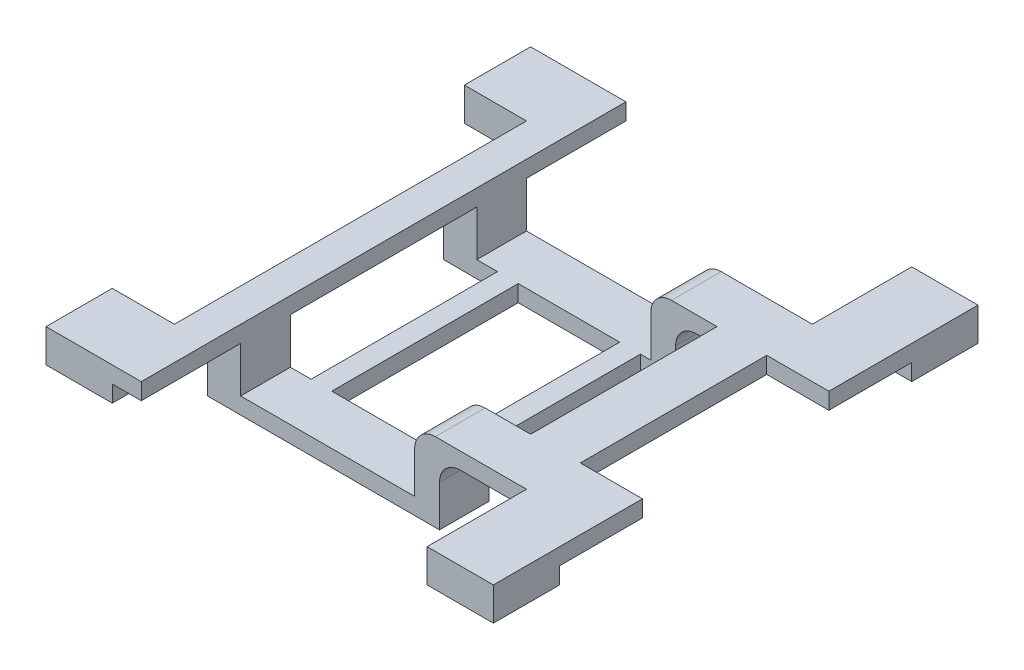
SolidWorks part; units mm, degrees
ref_plane "Front Plane" through (0, 0, 0) normal (0, 0, 1) x (1, 0, 0)
ref_plane "Top Plane" through (0, 0, 0) normal (0, 1, 0) x (1, 0, 0)
ref_plane "Right Plane" through (0, 0, 0) normal (1, 0, 0) x (0, 0, -1)
sketch "Sketch1" plane through (0, 0, 0) normal (0, 1, 0) x (1, 0, 0)
  line L1 (-56.5, 42.5) -> (56.5, 42.5)
  line L2 (-56.5, 42.5) -> (-56.5, -42.5)
  line L3 (-56.5, -42.5) -> (56.5, -42.5)
  line L4 (56.5, 42.5) -> (56.5, -42.5)
  line L5 (-56.5, 42.5) -> (56.5, -42.5) construction
  line L6 (-56.5, -42.5) -> (56.5, 42.5) construction
  point P0 (0, 0)
  dimension "D1" = 113
  dimension "D2" = 85
extrude "Boss-Extrude1" add sketch "Sketch1" along normal blind 4
sketch "Sketch4" plane through (0, 0, 0) normal (0, -1, 0) x (1, 0, 0)
  line L0 (-56.5, 42.5) -> (56.5, 42.5) construction
  line L5 (-56.5, 42.5) -> (-40.5, 42.5)
  line L6 (-56.5, 42.5) -> (-56.5, 58.5)
  line L7 (-56.5, 58.5) -> (-40.5, 58.5)
  line L8 (-40.5, 42.5) -> (-40.5, 58.5)
  line L9 (51.5, 42.5) -> (35.5, 42.5)
  line L10 (51.5, 42.5) -> (51.5, 58.5)
  line L11 (51.5, 58.5) -> (35.5, 58.5)
  line L12 (35.5, 42.5) -> (35.5, 58.5)
  line L18 (56.5, 42.5) -> (56.5, -42.5) construction
  line L19 (0, 0) -> (-56.5, 0) construction
  line L20 (-56.5, -42.5) -> (-56.5, 42.5) construction
  line L21 (51.5, -58.5) -> (35.5, -58.5)
  line L22 (35.5, -42.5) -> (35.5, -58.5)
  line L23 (51.5, -42.5) -> (35.5, -42.5)
  line L24 (51.5, -42.5) -> (51.5, -58.5)
  line L25 (-56.5, -58.5) -> (-40.5, -58.5)
  line L26 (-40.5, -42.5) -> (-40.5, -58.5)
  line L27 (-56.5, -42.5) -> (-40.5, -42.5)
  line L28 (-56.5, -42.5) -> (-56.5, -58.5)
  dimension "D1" = 16
  dimension "D2" = 16
  dimension "D3" = 5
  dimension "D4" = 16
  dimension "D5" = 16
extrude "Boss-Extrude3" add sketch "Sketch4" against normal up to surface (4 mm away) and the other way blind 1 up to face at (0, 4, 0)
sketch "Sketch10" plane through (0, 4, 0) normal (0, 1, 0) x (1, 0, 0)
  line L0 (-40.5, -58.5) -> (-56.5, -58.5) construction
  line L1 (-40.5, -42.5) -> (-30.5, -42.5)
  line L2 (-40.5, -42.5) -> (-40.5, -58.5)
  line L3 (-40.5, -58.5) -> (-30.5, -58.5)
  line L4 (-30.5, -42.5) -> (-30.5, -58.5)
  line L5 (-40.5, 42.5) -> (-30.5, 42.5)
  line L6 (-40.5, 42.5) -> (-40.5, 58.5)
  line L7 (-40.5, 58.5) -> (-30.5, 58.5)
  line L8 (-30.5, 42.5) -> (-30.5, 58.5)
  line L9 (-56.5, 58.5) -> (-40.5, 58.5) construction
  dimension "D1" = 10
  dimension "D2" = 10
extrude "Boss-Extrude6" add sketch "Sketch10" against normal up to surface (4 mm away) up to face at (9.3, 0, 0)
sketch "Sketch6" plane through (0, 4, 0) normal (0, 1, 0) x (1, 0, 0)
  line L0 (35.5, 42.5) -> (35.5, 58.5) construction
  line L1 (-31.5, 22.5) -> (41.5, 22.5)
  line L2 (-31.5, 22.5) -> (-31.5, -22.5)
  line L3 (-31.5, -22.5) -> (41.5, -22.5)
  line L4 (41.5, 22.5) -> (41.5, -22.5)
  line L5 (35.5, -58.5) -> (35.5, -42.5) construction
  line L6 (35.5, 42.5) -> (-30.5, 42.5) construction
  line L7 (-30.5, -42.5) -> (35.5, -42.5) construction
  line L8 (-56.5, 58.5) -> (-56.5, -58.5) construction
  line L9 (-41.5, 0) -> (-56.5, 0) construction
  line L10 (-56.5, 42.5) -> (-41.5, 42.5)
  line L11 (-56.5, 42.5) -> (-56.5, -42.5)
  line L12 (-56.5, -42.5) -> (-41.5, -42.5)
  line L13 (-41.5, 42.5) -> (-41.5, -42.5)
  line L14 (-31.5, 0) -> (41.5, 0) construction
  line L15 (-30.5, 42.5) -> (35.5, 42.5)
  line L16 (-30.5, 42.5) -> (-30.5, 34.5)
  line L17 (-30.5, 34.5) -> (35.5, 34.5)
  line L18 (35.5, 42.5) -> (35.5, 34.5)
  line L19 (-30.5, -42.5) -> (35.5, -42.5)
  line L20 (-30.5, -42.5) -> (-30.5, -34.5)
  line L21 (-30.5, -34.5) -> (35.5, -34.5)
  line L22 (35.5, -42.5) -> (35.5, -34.5)
  line L23 (56.5, -42.5) -> (56.5, 42.5) construction
  dimension "D1" = 20
  dimension "D2" = 20
  dimension "D3" = 25
  dimension "D4" = 15
  dimension "D5" = 85
  dimension "D6" = 8
  dimension "D7" = 8
  dimension "D8" = 15
extrude "Cut-Extrude2" cut sketch "Sketch6" against normal through all
sketch "Sketch8" plane through (0, -1, 0) normal (0, -1, 0) x (1, 0, 0)
  line L0 (-56.5, 58.5) -> (-40.5, 58.5) construction
  line L1 (-56.5, 58.5) -> (-56.5, 42.5) construction
  line L2 (-56.5, 42.5) -> (-40.5, 42.5) construction
  line L3 (-40.5, 58.5) -> (-40.5, 42.5) construction
  line L4 (35.5, 58.5) -> (51.5, 58.5) construction
  line L5 (35.5, 58.5) -> (35.5, 42.5) construction
  line L6 (35.5, 42.5) -> (51.5, 42.5) construction
  line L7 (51.5, 58.5) -> (51.5, 42.5) construction
  line L8 (-56.5, 58.5) -> (-40.5, 42.5) construction
  line L9 (-56.5, 42.5) -> (-40.5, 58.5) construction
  line L10 (35.5, 58.5) -> (51.5, 42.5) construction
  line L11 (35.5, 42.5) -> (51.5, 58.5) construction
  line L12 (51.5, 58.5) -> (35.5, 58.5) construction
  line L13 (0, 0) -> (-56.5, 0) construction
  line L14 (-56.5, 42.5) -> (-40.5, 42.5) construction
  line L15 (35.5, 42.5) -> (51.5, 42.5) construction
  circle A0 centre (-48.5, 50.5) radius 6.1
  circle A1 centre (43.5, 50.5) radius 6.1
  circle A2 centre (43.5, -50.5) radius 6.1
  circle A3 centre (-48.5, -50.5) radius 6.1
  dimension "D3" = 12.2
  dimension "D4" = 12.2
extrude "Cut-Extrude3" cut sketch "Sketch8" against normal blind 3.2
sketch "Sketch9" plane through (0, -1, 0) normal (0, -1, 0) x (1, 0, 0)
  line L0 (-55.5, 57.5) -> (-55.5, 43.5)
  line L1 (-56.5, 58.5) -> (-40.5, 58.5)
  line L2 (-56.5, 58.5) -> (-56.5, 42.5)
  line L3 (-56.5, 42.5) -> (-40.5, 42.5)
  line L4 (-40.5, 58.5) -> (-40.5, 42.5)
  line L5 (35.5, 58.5) -> (51.5, 58.5)
  line L6 (35.5, 58.5) -> (35.5, 42.5)
  line L7 (35.5, 42.5) -> (51.5, 42.5)
  line L8 (51.5, 58.5) -> (51.5, 42.5)
  line L9 (-55.5, 43.5) -> (-41.5, 43.5)
  line L10 (-41.5, 57.5) -> (-41.5, 43.5)
  line L11 (-55.5, 57.5) -> (-41.5, 57.5)
  line L16 (0, 0) -> (-56.5, 0) construction
  line L17 (36.5, -43.5) -> (50.5, -43.5)
  line L18 (36.5, -57.5) -> (36.5, -43.5)
  line L19 (50.5, -57.5) -> (36.5, -57.5)
  line L20 (50.5, 43.5) -> (50.5, 57.5)
  line L21 (50.5, 57.5) -> (36.5, 57.5)
  line L22 (36.5, 57.5) -> (36.5, 43.5)
  line L23 (36.5, 43.5) -> (50.5, 43.5)
  line L24 (50.5, 43.5) -> (50.5, 57.5)
  line L25 (50.5, 57.5) -> (36.5, 57.5)
  line L26 (36.5, 57.5) -> (36.5, 43.5)
  line L27 (36.5, 43.5) -> (50.5, 43.5)
  line L28 (50.5, -43.5) -> (50.5, -57.5)
  line L29 (-55.5, -57.5) -> (-41.5, -57.5)
  line L30 (-41.5, -57.5) -> (-41.5, -43.5)
  line L31 (-55.5, -43.5) -> (-41.5, -43.5)
  line L32 (51.5, -58.5) -> (51.5, -42.5)
  line L33 (35.5, -42.5) -> (51.5, -42.5)
  line L34 (35.5, -58.5) -> (35.5, -42.5)
  line L35 (35.5, -58.5) -> (51.5, -58.5)
  line L36 (-40.5, -58.5) -> (-40.5, -42.5)
  line L37 (-56.5, -42.5) -> (-40.5, -42.5)
  line L38 (-56.5, -58.5) -> (-56.5, -42.5)
  line L39 (-56.5, -58.5) -> (-40.5, -58.5)
  line L40 (-55.5, -57.5) -> (-55.5, -43.5)
  dimension "D1" = 1
  dimension "D2" = 1
extrude "Boss-Extrude5" add sketch "Sketch9" along normal blind 3
fillet "Fillet1" radius 0.2 4 edges at (43.5, -1, -44.4) (-48.5, -1, -44.4) (43.5, -1, 44.4) (-48.5, -1, 44.4)
sketch "Sketch13" plane through (56.5, 0, 0) normal (1, 0, 0) x (0, 0, -1)
  line L1 (-42.5, 4) -> (42.5, 4)
  line L2 (-42.5, 4) -> (-42.5, 0)
  line L3 (-42.5, 0) -> (42.5, 0)
  line L4 (42.5, 4) -> (42.5, 0)
extrude "Cut-Extrude4" cut sketch "Sketch13" against normal up to surface (5 mm away) up to face at (51.5, 0, 48.9)
sketch "Sketch14" plane through (0, 4, 0) normal (0, 1, 0) x (1, 0, 0)
  line L0 (-41.5, -42.5) -> (-41.5, 42.5) construction
  line L1 (-41.5, 22.5) -> (51.5, 22.5)
  line L2 (-41.5, 22.5) -> (-41.5, -22.5)
  line L3 (-41.5, -22.5) -> (51.5, -22.5)
  line L4 (51.5, 22.5) -> (51.5, -22.5)
  line L5 (51.5, 58.5) -> (51.5, -58.5) construction
  line L6 (-31.5, -22.5) -> (41.5, -22.5) construction
  line L7 (41.5, 22.5) -> (-31.5, 22.5) construction
extrude "Cut-Extrude5" cut sketch "Sketch14" against normal through all
sketch "Sketch15" plane through (0, 4, 0) normal (0, 1, 0) x (1, 0, 0)
  line L0 (51.5, 22.5) -> (-41.5, 22.5) construction
  line L1 (-28.5, 22.5) -> (-23.5, 22.5)
  line L2 (-28.5, 22.5) -> (-28.5, -22.5)
  line L3 (-28.5, -22.5) -> (-23.5, -22.5)
  line L4 (-23.5, 22.5) -> (-23.5, -22.5)
  line L5 (-41.5, -22.5) -> (51.5, -22.5) construction
  line L6 (51.5, -22.5) -> (51.5, -58.5) construction
  line L7 (24.5, 22.5) -> (36.5, 22.5)
  line L8 (24.5, 22.5) -> (24.5, -22.5)
  line L9 (24.5, -22.5) -> (36.5, -22.5)
  line L10 (36.5, 22.5) -> (36.5, -22.5)
  line L11 (-41.5, -42.5) -> (-41.5, -22.5) construction
  dimension "D1" = 5
  dimension "D2" = 12
  dimension "D3" = 15
  dimension "D4" = 13
extrude "Boss-Extrude7" add sketch "Sketch15" against normal up to surface (4 mm away) up to face at (-5.1, 0, 40.1)
sketch "Sketch16" plane through (0, 0, 0) normal (0, -1, 0) x (1, 0, 0)
  line L24 (24.5, 22.5) -> (24.5, -22.5) construction
  line L25 (24.5, -22.5) -> (-23.5, -22.5) construction
  line L26 (-23.5, -22.5) -> (-23.5, 22.5) construction
  line L27 (-23.5, 22.5) -> (24.5, 22.5) construction
  line L28 (24.5, 22.5) -> (24.5, -22.5) construction
  line L29 (24.5, -22.5) -> (-23.5, -22.5) construction
  line L30 (-23.5, -22.5) -> (-23.5, 22.5)
  line L31 (-23.5, 22.5) -> (24.5, 22.5) construction
  line L36 (-30.5, -34.5) -> (14.5, -34.5)
  line L37 (14.5, -34.5) -> (14.5, -22.5)
  line L38 (14.5, -22.5) -> (-23.5, -22.5)
  line L39 (-23.5, 22.5) -> (14.5, 22.5)
  line L40 (14.5, 22.5) -> (14.5, 34.5)
  line L41 (14.5, 34.5) -> (-30.5, 34.5)
  line L42 (-28.5, 22.5) -> (-41.5, 22.5)
  line L43 (-41.5, 22.5) -> (-28.5, 22.5) construction
  line L44 (-41.5, 22.5) -> (-41.5, 34.5)
  line L45 (-41.5, 34.5) -> (-30.5, 34.5)
  line L46 (-28.5, -22.5) -> (-41.5, -22.5)
  line L47 (-28.5, -22.5) -> (-41.5, -22.5) construction
  line L48 (-41.5, 42.5) -> (-41.5, 22.5)
  line L49 (-41.5, 22.5) -> (-28.5, 22.5)
  line L50 (-28.5, 22.5) -> (-28.5, -22.5)
  line L51 (-28.5, -22.5) -> (-41.5, -22.5)
  line L52 (-41.5, -22.5) -> (-41.5, -42.5)
  line L53 (-41.5, -42.5) -> (-40.5, -42.5)
  line L54 (-40.5, -42.5) -> (-40.5, -58.5)
  line L55 (-40.5, -58.5) -> (-30.5, -58.5)
  line L56 (-30.5, -58.5) -> (-30.5, -34.5)
  line L57 (-30.5, -34.5) -> (35.5, -34.5)
  line L58 (35.5, -34.5) -> (35.5, -42.5)
  line L59 (35.5, -42.5) -> (51.5, -42.5)
  line L60 (51.5, -42.5) -> (51.5, -22.5)
  line L61 (51.5, -22.5) -> (36.5, -22.5)
  line L62 (36.5, -22.5) -> (36.5, 22.5)
  line L63 (36.5, 22.5) -> (51.5, 22.5)
  line L64 (51.5, 22.5) -> (51.5, 42.5)
  line L65 (51.5, 42.5) -> (35.5, 42.5)
  line L66 (35.5, 42.5) -> (35.5, 34.5)
  line L67 (35.5, 34.5) -> (-30.5, 34.5)
  line L68 (-30.5, 34.5) -> (-30.5, 58.5)
  line L69 (-30.5, 58.5) -> (-40.5, 58.5)
  line L70 (-40.5, 58.5) -> (-40.5, 42.5)
  line L71 (-40.5, 42.5) -> (-41.5, 42.5)
  line L72 (-41.5, 42.5) -> (-41.5, 22.5) construction
  line L74 (-28.5, 22.5) -> (-28.5, -22.5)
  line L76 (-41.5, -22.5) -> (-41.5, -42.5) construction
  line L77 (-41.5, -42.5) -> (-40.5, -42.5) construction
  line L78 (-40.5, -42.5) -> (-40.5, -58.5) construction
  line L79 (-40.5, -58.5) -> (-30.5, -58.5) construction
  line L80 (-30.5, -58.5) -> (-30.5, -34.5) construction
  line L81 (-30.5, -34.5) -> (35.5, -34.5) construction
  line L82 (35.5, -34.5) -> (35.5, -42.5) construction
  line L83 (35.5, -42.5) -> (51.5, -42.5) construction
  line L84 (51.5, -42.5) -> (51.5, -22.5) construction
  line L85 (51.5, -22.5) -> (36.5, -22.5) construction
  line L86 (36.5, -22.5) -> (36.5, 22.5) construction
  line L87 (36.5, 22.5) -> (51.5, 22.5) construction
  line L88 (51.5, 22.5) -> (51.5, 42.5) construction
  line L89 (51.5, 42.5) -> (35.5, 42.5) construction
  line L90 (35.5, 42.5) -> (35.5, 34.5) construction
  line L91 (35.5, 34.5) -> (-30.5, 34.5) construction
  line L92 (-30.5, 34.5) -> (-30.5, 58.5) construction
  line L93 (-30.5, 58.5) -> (-40.5, 58.5) construction
  line L94 (-40.5, 58.5) -> (-40.5, 42.5) construction
  line L95 (-40.5, 42.5) -> (-41.5, 42.5) construction
  line L96 (-41.5, -22.5) -> (-41.5, -34.5)
  line L97 (-41.5, -34.5) -> (-30.5, -34.5)
  dimension "D2" = 45
  dimension "D1" = 0
extrude "Boss-Extrude8" add sketch "Sketch16" along normal blind 15
sketch "Sketch17" plane through (0, 4, 0) normal (0, 1, 0) x (1, 0, 0)
  line L0 (-30.5, -58.5) -> (-56.5, -58.5) construction
  line L1 (-33.5, 58.5) -> (8.5, 58.5)
  line L2 (-33.5, 58.5) -> (-33.5, -58.5)
  line L3 (-33.5, -58.5) -> (8.5, -58.5)
  line L4 (8.5, 58.5) -> (8.5, -58.5)
  line L7 (-41.5, 22.5) -> (-41.5, 42.5) construction
  line L8 (-56.5, 58.5) -> (-30.5, 58.5) construction
  dimension "D1" = 8
  dimension "D2" = 42
extrude "Cut-Extrude6" cut sketch "Sketch17" against normal blind 15
sketch "Sketch18" plane through (0, 4, 0) normal (0, 1, 0) x (1, 0, 0)
  line L1 (-33.5, 22.5) -> (-41.5, 22.5)
  line L2 (-33.5, 22.5) -> (-33.5, -22.5)
  line L3 (-33.5, -22.5) -> (-41.5, -22.5)
  line L4 (-41.5, 22.5) -> (-41.5, -22.5)
extrude "Boss-Extrude9" add sketch "Sketch18" against normal blind 4
fillet "Fillet2" radius 5 4 edges at (8.5, 4, -28.5) (8.5, 4, 28.5) (14.5, 0, 28.5) (14.5, 0, -28.5)
sketch "Sketch19" plane through (0, -11, 0) normal (0, 1, 0) x (1, 0, 0)
  line L0 (-23.5, 22.5) -> (8.5, 22.5) construction
  line L1 (1, 22.5) -> (6, 22.5)
  line L2 (1, 22.5) -> (1, -22.5)
  line L3 (1, -22.5) -> (6, -22.5)
  line L4 (6, 22.5) -> (6, -22.5)
  line L5 (8.5, -22.5) -> (-23.5, -22.5) construction
  line L6 (8.5, -34.5) -> (8.5, -22.5) construction
  dimension "D1" = 5
  dimension "D2" = 2.5
extrude "Boss-Extrude10" add sketch "Sketch19" against normal up to surface (4 mm away) up to face at (-17.6667, -15, 0)
